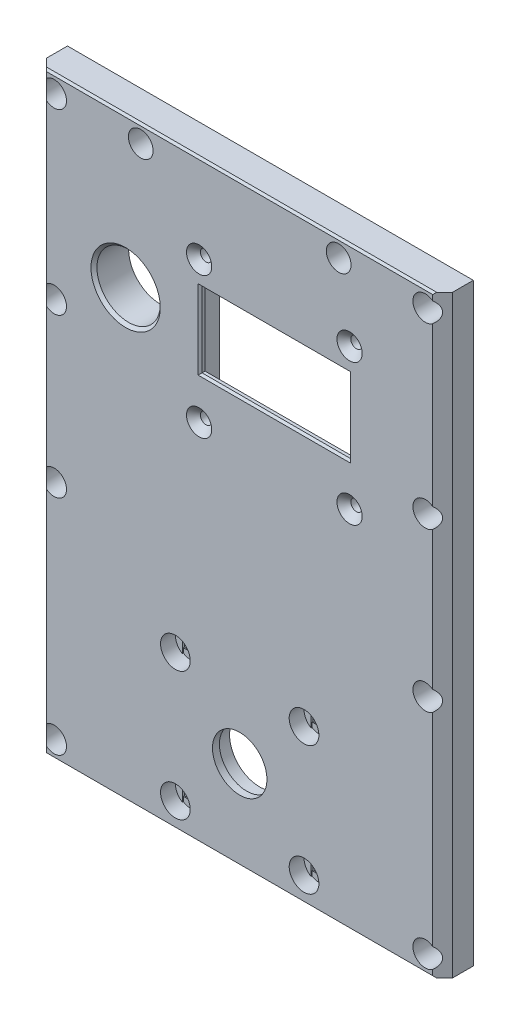
SolidWorks part; units mm, degrees
ref_plane "Front Plane" through (0, 0, 0) normal (0, 0, 1) x (1, 0, 0)
ref_plane "Top Plane" through (0, 0, 0) normal (0, 1, 0) x (1, 0, 0)
ref_plane "Right Plane" through (0, 0, 0) normal (1, 0, 0) x (0, 0, -1)
sketch "Sketch1" plane through (0, 0, 0) normal (0, 0, 1) x (1, 0, 0)
  line L1 (-41, -60) -> (41, -60)
  line L2 (-41, -60) -> (-41, 60)
  line L3 (-41, 60) -> (41, 60)
  line L4 (41, -60) -> (41, 60)
  line L5 (-41, -60) -> (41, 60) construction
  line L6 (-41, 60) -> (41, -60) construction
  line L7 (-34, -53) -> (34, -53)
  line L8 (-34, -53) -> (-34, 53)
  line L9 (-34, 53) -> (34, 53)
  line L10 (34, -53) -> (34, 53)
  line L11 (-34, -53) -> (34, 53) construction
  line L12 (-34, 53) -> (34, -53) construction
  point P0 (0, 0)
  point P6 (0, 0)
  dimension "D1" = 120
  dimension "D2" = 82
  dimension "D3" = 7
  dimension "D4" = 7
extrude "Boss-Extrude1" add sketch "Sketch1" along normal blind 7
sketch "Sketch2" plane through (0, 0, 7) normal (0, 0, 1) x (1, 0, 0)
  line L0 (34, -53) -> (34, 53) construction
  line L1 (-34, -53) -> (34, -53)
  line L2 (-34, -53) -> (-34, -17)
  line L3 (-34, -17) -> (34, -17)
  line L4 (34, -53) -> (34, -17)
  dimension "D1" = 36
extrude "Boss-Extrude2" add sketch "Sketch2" against normal up to surface (7 mm away) up to face at (0, 0, 0)
sketch "Sketch3" plane through (0, 0, 0) normal (0, 0, -1) x (-1, 0, 0)
  line L0 (0, -60) -> (0, -42) construction
  line L1 (41, -60) -> (-41, -60) construction
  circle A0 centre (0, -42) radius 5.5
  dimension "D1" = 11
  dimension "D2" = 18
extrude "Cut-Extrude1" cut sketch "Sketch3" against normal through all
sketch "Sketch4" plane through (0, 0, 0) normal (0, 0, -1) x (-1, 0, 0)
  circle A0 centre (0, -42) radius 6.05
  dimension "D1" = 12.1
extrude "Cut-Extrude2" cut sketch "Sketch4" against normal offset from surface (5.6 mm away) 1.4 up to face at (-5.5, -42, 7)
sketch "Sketch5" plane through (0, 0, 0) normal (0, 0, -1) x (-1, 0, 0)
  circle A0 centre (0, -42) radius 11.1
  dimension "D1" = 22.2
extrude "Cut-Extrude3" cut sketch "Sketch5" against normal offset from surface (3 mm away) 2.6 up to face at (-6.05, -42, 5.6)
sketch "Sketch6" plane through (0, 0, 0) normal (0, 0, -1) x (-1, 0, 0)
  line L1 (-13, -55) -> (13, -55) construction
  line L2 (-13, -55) -> (-13, -29) construction
  line L3 (-13, -29) -> (13, -29) construction
  line L4 (13, -55) -> (13, -29) construction
  line L5 (-13, -55) -> (13, -29) construction
  line L6 (-13, -29) -> (13, -55) construction
  circle A0 centre (-13, -29) radius 1.6
  circle A1 centre (13, -29) radius 1.6
  circle A2 centre (13, -55) radius 1.6
  circle A3 centre (-13, -55) radius 1.6
  point P0 (0, -42)
  dimension "D2" = 3.2
  dimension "D1" = 26
extrude "Cut-Extrude4" cut sketch "Sketch6" against normal through all
sketch "Sketch7" plane through (0, 0, 0) normal (0, 0, -1) x (-1, 0, 0)
  line L1 (-25, -61) -> (25, -61)
  line L2 (-25, -61) -> (-25, -23)
  line L3 (-25, -23) -> (25, -23)
  line L4 (25, -61) -> (25, -23)
  line L5 (-25, -61) -> (25, -23) construction
  line L6 (-25, -23) -> (25, -61) construction
  point P0 (0, -42)
  dimension "D1" = 50
  dimension "D2" = 38
extrude "Cut-Extrude5" cut sketch "Sketch7" against normal blind 1
sketch "Sketch8" plane through (0, 0, 7) normal (0, 0, 1) x (1, 0, 0)
  circle A0 centre (-13, -29) radius 3
  circle A1 centre (13, -29) radius 3
  circle A2 centre (13, -55) radius 3
  circle A3 centre (-13, -55) radius 3
  dimension "D1" = 6
extrude "Cut-Extrude6" cut sketch "Sketch8" against normal blind 3
sketch "Sketch9" plane through (0, 0, 7) normal (0, 0, 1) x (1, 0, 0)
  line L0 (-41, 60) -> (-41, -60) construction
  line L1 (-37.5, -56.5) -> (37.5, -56.5) construction
  line L2 (-37.5, -56.5) -> (-37.5, 56.5) construction
  line L3 (-37.5, 56.5) -> (37.5, 56.5) construction
  line L4 (37.5, -56.5) -> (37.5, 56.5) construction
  line L5 (-37.5, -56.5) -> (37.5, 56.5) construction
  line L6 (-37.5, 56.5) -> (37.5, -56.5) construction
  line L7 (41, 60) -> (-41, 60) construction
  circle A0 centre (-37.5, 56.5) radius 1.45
  circle A1 centre (37.5, 56.5) radius 1.45
  circle A2 centre (37.5, -56.5) radius 1.45
  circle A3 centre (-37.5, -56.5) radius 1.45
  circle A6 centre (-37.5, 20.5) radius 1.45
  circle A7 centre (-37.5, -11.5) radius 1.45
  circle A8 centre (37.5, -11.5) radius 1.45
  circle A9 centre (37.5, 20.5) radius 1.45
  point P0 (0, 0)
  dimension "D3" = 2.9
  dimension "D4" = 45
  dimension "D5" = 36
  dimension "D1" = 3.5
  dimension "D2" = 3.5
extrude "Cut-Extrude7" cut sketch "Sketch9" against normal through all
sketch "Sketch10" plane through (0, 0, 7) normal (0, 0, 1) x (1, 0, 0)
  circle A0 centre (-37.5, 56.5) radius 2.5
  circle A1 centre (37.5, 56.5) radius 2.5
  circle A2 centre (-37.5, 20.5) radius 2.5
  circle A3 centre (-37.5, -11.5) radius 2.5
  circle A4 centre (-37.5, -56.5) radius 2.5
  circle A5 centre (37.5, -56.5) radius 2.5
  circle A6 centre (37.5, 20.5) radius 2.5
  circle A7 centre (37.5, -11.5) radius 2.5
  dimension "D1" = 5
extrude "Cut-Extrude8" cut sketch "Sketch10" against normal blind 5
chamfer "Chamfer1" distance 2 angle 45 2 edges at (-41, 0, 7) (41, 0, 7)
sketch "Sketch11" plane through (0, 0, 7) normal (0, 0, 1) x (1, 0, 0)
  line L0 (34, -17) -> (34, 53) construction
  line L1 (-34, -17) -> (34, -17)
  line L2 (-34, -17) -> (-34, 2)
  line L3 (-34, 2) -> (34, 2)
  line L4 (34, -17) -> (34, 2)
  line L5 (-39, -60) -> (39, -60) construction
  dimension "D1" = 62
extrude "Boss-Extrude3" add sketch "Sketch11" against normal up to surface (7 mm away) up to face at (38.95, 56.5, 0)
sketch "Sketch12" plane through (0, 0, 2) normal (0, 0, 1) x (1, 0, 0)
  line L2 (-38.95, -58.5365) -> (-38.95, -54.4635)
  line L4 (-36.05, -58.5365) -> (-36.05, -54.4635)
  line L5 (-38.95, -58.5365) -> (-36.05, -54.4635) construction
  line L6 (-38.95, -54.4635) -> (-36.05, -58.5365) construction
  line L8 (-38.95, -13.5365) -> (-38.95, -9.4635)
  line L10 (-36.05, -13.5365) -> (-36.05, -9.4635)
  line L11 (-38.95, -13.5365) -> (-36.05, -9.4635) construction
  line L12 (-38.95, -9.4635) -> (-36.05, -13.5365) construction
  line L14 (-38.95, 18.4635) -> (-38.95, 22.5365)
  line L16 (-36.05, 18.4635) -> (-36.05, 22.5365)
  line L17 (-38.95, 18.4635) -> (-36.05, 22.5365) construction
  line L18 (-38.95, 22.5365) -> (-36.05, 18.4635) construction
  line L20 (-38.95, 54.4635) -> (-38.95, 58.5365)
  line L22 (-36.05, 54.4635) -> (-36.05, 58.5365)
  line L23 (-38.95, 54.4635) -> (-36.05, 58.5365) construction
  line L24 (-38.95, 58.5365) -> (-36.05, 54.4635) construction
  arc A0 (-39, -58.5) -> (-39, -54.5) centre (-37.5, -56.5) ccw construction
  circle A1 centre (-37.5, -11.5) radius 2.5 construction
  circle A2 centre (-37.5, 20.5) radius 2.5 construction
  arc A3 (-39, 54.5) -> (-39, 58.5) centre (-37.5, 56.5) ccw construction
  circle A4 centre (-37.5, 56.5) radius 1.45 construction
  circle A5 centre (-37.5, 56.5) radius 2.5 construction
  arc A6 (-36.05, 58.5365) -> (-38.95, 58.5365) centre (-37.5, 56.5) ccw
  arc A7 (-38.95, 54.4635) -> (-36.05, 54.4635) centre (-37.5, 56.5) ccw
  circle A8 centre (-37.5, 20.5) radius 1.45 construction
  arc A9 (-38.95, 18.4635) -> (-36.05, 18.4635) centre (-37.5, 20.5) ccw
  arc A10 (-36.05, 22.5365) -> (-38.95, 22.5365) centre (-37.5, 20.5) ccw
  circle A11 centre (-37.5, -11.5) radius 1.45 construction
  arc A12 (-38.95, -13.5365) -> (-36.05, -13.5365) centre (-37.5, -11.5) ccw
  arc A13 (-36.05, -9.4635) -> (-38.95, -9.4635) centre (-37.5, -11.5) ccw
  circle A14 centre (-37.5, -56.5) radius 1.45 construction
  arc A16 (-38.95, -58.5365) -> (-36.05, -58.5365) centre (-37.5, -56.5) ccw
  arc A18 (-36.05, -54.4635) -> (-38.95, -54.4635) centre (-37.5, -56.5) ccw
  point P0 (-37.5, -56.5)
  point P9 (-37.5, -11.5)
  point P17 (-37.5, 20.5)
  point P25 (-37.5, 56.5)
extrude "Cut-Extrude9" cut sketch "Sketch12" against normal blind 0.2
sketch "Sketch13" plane through (0, 0, 1.8) normal (0, 0, 1) x (1, 0, 0)
  line L0 (-36.05, -56.5) -> (-36.05, -54.4635) construction
  line L1 (-38.95, -57.95) -> (-36.05, -57.95)
  line L2 (-38.95, -57.95) -> (-38.95, -55.05)
  line L3 (-38.95, -55.05) -> (-36.05, -55.05)
  line L4 (-36.05, -57.95) -> (-36.05, -55.05)
  line L5 (-38.95, -57.95) -> (-36.05, -55.05) construction
  line L6 (-38.95, -55.05) -> (-36.05, -57.95) construction
  line L7 (-36.05, -11.5) -> (-36.05, -9.4635) construction
  line L8 (-38.95, -12.95) -> (-36.05, -12.95)
  line L9 (-38.95, -12.95) -> (-38.95, -10.05)
  line L10 (-38.95, -10.05) -> (-36.05, -10.05)
  line L11 (-36.05, -12.95) -> (-36.05, -10.05)
  line L12 (-38.95, -12.95) -> (-36.05, -10.05) construction
  line L13 (-38.95, -10.05) -> (-36.05, -12.95) construction
  line L14 (-36.05, 18.4635) -> (-36.05, 22.5365) construction
  line L15 (-38.95, 19.05) -> (-36.05, 19.05)
  line L16 (-38.95, 19.05) -> (-38.95, 21.95)
  line L17 (-38.95, 21.95) -> (-36.05, 21.95)
  line L18 (-36.05, 19.05) -> (-36.05, 21.95)
  line L19 (-38.95, 19.05) -> (-36.05, 21.95) construction
  line L20 (-38.95, 21.95) -> (-36.05, 19.05) construction
  line L21 (-36.05, 54.4635) -> (-36.05, 58.5365) construction
  line L22 (-38.95, 55.05) -> (-36.05, 55.05)
  line L23 (-38.95, 55.05) -> (-38.95, 57.95)
  line L24 (-38.95, 57.95) -> (-36.05, 57.95)
  line L25 (-36.05, 55.05) -> (-36.05, 57.95)
  line L26 (-38.95, 55.05) -> (-36.05, 57.95) construction
  line L27 (-38.95, 57.95) -> (-36.05, 55.05) construction
  arc A0 (-36.05, -56.5) -> (-38.95, -56.5) centre (-37.5, -56.5) ccw construction
  arc A1 (-36.05, -11.5) -> (-38.95, -11.5) centre (-37.5, -11.5) ccw construction
  arc A2 (-36.05, 20.5) -> (-38.95, 20.5) centre (-37.5, 20.5) ccw construction
  arc A3 (-36.05, 56.5) -> (-38.95, 56.5) centre (-37.5, 56.5) ccw construction
  point P0 (-37.5, -56.5)
  point P11 (-37.5, -11.5)
  point P22 (-37.5, 20.5)
  point P33 (-37.5, 56.5)
extrude "Cut-Extrude10" cut sketch "Sketch13" against normal blind 0.2
sketch "Sketch14" plane through (0, 0, 4) normal (0, 0, 1) x (1, 0, 0)
  line L2 (-14.6, -31.5377) -> (-14.6, -26.4623)
  line L4 (-11.4, -31.5377) -> (-11.4, -26.4623)
  line L5 (-14.6, -31.5377) -> (-11.4, -26.4623) construction
  line L6 (-14.6, -26.4623) -> (-11.4, -31.5377) construction
  line L8 (-14.6, -57.5377) -> (-14.6, -52.4623)
  line L10 (-11.4, -57.5377) -> (-11.4, -52.4623)
  line L11 (-14.6, -57.5377) -> (-11.4, -52.4623) construction
  line L12 (-14.6, -52.4623) -> (-11.4, -57.5377) construction
  circle A0 centre (-13, -29) radius 3 construction
  circle A1 centre (-13, -55) radius 3 construction
  circle A2 centre (-13, -29) radius 3 construction
  arc A3 (-14.6, -31.5377) -> (-11.4, -31.5377) centre (-13, -29) ccw
  arc A4 (-14.6, -57.5377) -> (-11.4, -57.5377) centre (-13, -55) ccw
  circle A5 centre (-13, -29) radius 1.6 construction
  circle A6 centre (-13, -55) radius 1.6 construction
  arc A7 (-11.4, -26.4623) -> (-14.6, -26.4623) centre (-13, -29) ccw
  arc A8 (-11.4, -52.4623) -> (-14.6, -52.4623) centre (-13, -55) ccw
  point P0 (-13, -29)
  point P8 (-13, -55)
extrude "Cut-Extrude11" cut sketch "Sketch14" against normal blind 0.2
sketch "Sketch15" plane through (0, 0, 3.8) normal (0, 0, 1) x (1, 0, 0)
  line L0 (-11.4, -29) -> (-11.4, -26.4623) construction
  line L1 (-14.6, -30.6) -> (-11.4, -30.6)
  line L2 (-14.6, -30.6) -> (-14.6, -27.4)
  line L3 (-14.6, -27.4) -> (-11.4, -27.4)
  line L4 (-11.4, -30.6) -> (-11.4, -27.4)
  line L5 (-14.6, -30.6) -> (-11.4, -27.4) construction
  line L6 (-14.6, -27.4) -> (-11.4, -30.6) construction
  line L7 (-11.4, -55) -> (-11.4, -52.4623) construction
  line L8 (-14.6, -56.6) -> (-11.4, -56.6)
  line L9 (-14.6, -56.6) -> (-14.6, -53.4)
  line L10 (-14.6, -53.4) -> (-11.4, -53.4)
  line L11 (-11.4, -56.6) -> (-11.4, -53.4)
  line L12 (-14.6, -56.6) -> (-11.4, -53.4) construction
  line L13 (-14.6, -53.4) -> (-11.4, -56.6) construction
  arc A0 (-11.4, -55) -> (-14.6, -55) centre (-13, -55) ccw construction
  arc A1 (-14.6, -29) -> (-11.4, -29) centre (-13, -29) ccw construction
  point P0 (-13, -29)
  point P8 (-13, -55)
extrude "Cut-Extrude12" cut sketch "Sketch15" against normal blind 0.2
mirror "Mirror1" about plane through (0, 0, 0) normal (1, 0, 0) of "Cut-Extrude10", "Cut-Extrude11", "Cut-Extrude12", "Cut-Extrude9"
chamfer "Chamfer2" distance 0.4 angle 45 4 edges at (34, 27.5, 7) (0, 53, 7) (0, 2, 7) (-34, 27.5, 7)
chamfer "Chamfer3" distance 0.8 angle 45 2 edges at (-41, 0, 0) (41, 0, 0)
sketch "Sketch16" plane through (0, 0, 0) normal (1, 0, 0) x (0, 0, -1)
  line L0 (0, -4) -> (0, -15.4)
  line L1 (0, 60) -> (0, -60) construction
  line L2 (0, -15.4) -> (3.2, -12.2)
  line L3 (3.2, -12.2) -> (3.2, -7.2)
  line L4 (3.2, -7.2) -> (0, -4)
  line L5 (0, -15.4) -> (0, -19.4) construction
  line L6 (0.6, -7.7) -> (2.6, -7.7)
  line L7 (0.6, -7.7) -> (0.6, -11.7)
  line L8 (0.6, -11.7) -> (2.6, -11.7)
  line L9 (2.6, -7.7) -> (2.6, -11.7)
  line L10 (-1.046, -17.4) -> (12.8392, -17.4) construction
  line L11 (2.6, -27.1) -> (2.6, -23.1)
  line L12 (0.6, -23.1) -> (2.6, -23.1)
  line L13 (0.6, -27.1) -> (0.6, -23.1)
  line L14 (0.6, -27.1) -> (2.6, -27.1)
  line L15 (3.2, -27.6) -> (0, -30.8)
  line L16 (3.2, -22.6) -> (3.2, -27.6)
  line L17 (0, -19.4) -> (3.2, -22.6)
  line L18 (0, -30.8) -> (0, -19.4)
  point P10 (2.6, -9.7)
  point P11 (3.2, -9.7)
  point P24 (0, -17.4)
  dimension "D1" = 5
  dimension "D2" = 2
  dimension "D3" = 0.6
  dimension "D4" = 0.6
  dimension "D5" = 45
  dimension "D6" = 4
  dimension "D7" = 4
  dimension "D8" = 4
extrude "Boss-Extrude4" add sketch "Sketch16" along normal mid plane 2
pattern_linear "LPattern1" count 2 spacing 20 along (1, 0, 0) count 2 spacing 20 along (-1, 0, 0) of "Boss-Extrude4"
sketch "Sketch17" plane through (0, 0, 0) normal (0, 0, -1) x (-1, 0, 0)
  line L0 (-20, 56.5) -> (20, 56.5) construction
  line L1 (-40.2, 60) -> (40.2, 60) construction
  circle A0 centre (-37.5, 56.5) radius 1.45 construction
  circle A1 centre (-37.5, 56.5) radius 1.45 construction
  circle A2 centre (-20, 56.5) radius 1.45
  circle A3 centre (20, 56.5) radius 1.45
  point P3 (0, 56.5)
  point P6 (0, 60)
  dimension "D1" = 40
extrude "Cut-Extrude13" cut sketch "Sketch17" against normal through all
sketch "Sketch18" plane through (0, 0, 7) normal (0, 0, 1) x (1, 0, 0)
  circle A0 centre (-20, 56.5) radius 2.5
  circle A1 centre (20, 56.5) radius 2.5
  arc A2 (-39, 54.5) -> (-39, 58.5) centre (-37.5, 56.5) ccw construction
extrude "Cut-Extrude14" cut sketch "Sketch18" against normal up to surface (5 mm away) up to face at (35.525, 56.5, 2)
sketch "Sketch19" plane through (0, 0, 2) normal (0, 0, 1) x (1, 0, 0)
  line L2 (-21.45, 54.4635) -> (-21.45, 58.5365)
  line L4 (-18.55, 54.4635) -> (-18.55, 58.5365)
  line L5 (-21.45, 54.4635) -> (-18.55, 58.5365) construction
  line L6 (-21.45, 58.5365) -> (-18.55, 54.4635) construction
  line L8 (18.55, 54.4635) -> (18.55, 58.5365)
  line L10 (21.45, 54.4635) -> (21.45, 58.5365)
  line L11 (18.55, 54.4635) -> (21.45, 58.5365) construction
  line L12 (18.55, 58.5365) -> (21.45, 54.4635) construction
  circle A0 centre (-20, 56.5) radius 2.5 construction
  circle A1 centre (20, 56.5) radius 2.5 construction
  circle A2 centre (20, 56.5) radius 1.45 construction
  circle A3 centre (-20, 56.5) radius 1.45 construction
  circle A4 centre (-20, 56.5) radius 2.5 construction
  arc A5 (18.55, 54.4635) -> (21.45, 54.4635) centre (20, 56.5) ccw
  arc A6 (-18.55, 58.5365) -> (-21.45, 58.5365) centre (-20, 56.5) ccw
  arc A7 (21.45, 58.5365) -> (18.55, 58.5365) centre (20, 56.5) ccw
  arc A8 (-21.45, 54.4635) -> (-18.55, 54.4635) centre (-20, 56.5) ccw
  point P0 (-20, 56.5)
  point P8 (20, 56.5)
extrude "Cut-Extrude15" cut sketch "Sketch19" against normal blind 0.2
sketch "Sketch20" plane through (0, 0, 1.8) normal (0, 0, 1) x (1, 0, 0)
  line L0 (-18.55, 54.4635) -> (-18.55, 58.5365) construction
  line L1 (-21.45, 55.05) -> (-18.55, 55.05)
  line L2 (-21.45, 55.05) -> (-21.45, 57.95)
  line L3 (-21.45, 57.95) -> (-18.55, 57.95)
  line L4 (-18.55, 55.05) -> (-18.55, 57.95)
  line L5 (-21.45, 55.05) -> (-18.55, 57.95) construction
  line L6 (-21.45, 57.95) -> (-18.55, 55.05) construction
  line L7 (21.45, 56.5) -> (21.45, 58.5365) construction
  line L8 (18.55, 55.05) -> (21.45, 55.05)
  line L9 (18.55, 55.05) -> (18.55, 57.95)
  line L10 (18.55, 57.95) -> (21.45, 57.95)
  line L11 (21.45, 55.05) -> (21.45, 57.95)
  line L12 (18.55, 55.05) -> (21.45, 57.95) construction
  line L13 (18.55, 57.95) -> (21.45, 55.05) construction
  arc A0 (18.55, 56.5) -> (21.45, 56.5) centre (20, 56.5) ccw construction
  point P0 (-20, 56.5)
  point P8 (20, 56.5)
extrude "Cut-Extrude16" cut sketch "Sketch20" against normal blind 0.2
sketch "Skizze4" plane through (0, 0, 0) normal (0, 0, -1) x (-1, 0, 0)
  line L1 (21, -4) -> (-21, -4)
  line L2 (21, -4) -> (21, -30.8)
  line L3 (21, -30.8) -> (-21, -30.8)
  line L4 (-21, -4) -> (-21, -30.8)
extrude "Schnitt-Linear austragen1" cut sketch "Skizze4" along normal up to surface (3.2 mm away) up to face at (-20, -9.7, -3.2)
sketch "Skizze6" plane through (0, 0, 7) normal (0, 0, 1) x (1, 0, 0)
  line L0 (12.4, 53.4) -> (34.4, 31.4) construction
  line L1 (34.4, 53.4) -> (12.4, 53.4)
  line L2 (34.4, 53.4) -> (34.4, 31.4)
  line L3 (34.4, 31.4) -> (12.4, 31.4)
  line L4 (12.4, 53.4) -> (12.4, 31.4)
  line L5 (23.4, 53.4) -> (23.4, 31.4) construction
  circle A0 centre (23.4, 41.4) radius 8.25
  point P10 (23.4, 42.4)
  dimension "D1" = 16.5
  dimension "D2" = 22
  dimension "D3" = 22
  dimension "D4" = 1
extrude "Aufsatz-Linear austragen1" add sketch "Skizze6" against normal up to surface (7 mm away) up to face at (0, -20.75, 0)
sketch "Skizze7" plane through (0, 0, 7) normal (0, 0, 1) x (1, 0, 0)
  circle A0 centre (23.4, 41.4) radius 9.25
  dimension "D1" = 18.5
extrude "Schnitt-Linear austragen2" cut sketch "Skizze7" against normal blind 1.6
chamfer "Fase6" distance 0.5 angle 45 2 edges at (12.4, 42.4, 7) (23.4, 31.4, 7)
chamfer "Fase7" distance 4 angle 45 1 edges at (12.4, 31.4, 3.25)
chamfer "Fase8" distance 1 angle 45 1 edges at (31.65, 41.4, 5.4)
mirror "Mirror2" about plane through (0, 0, 0) normal (1, 0, 0) of "Fase6", "Schnitt-Linear austragen2", "Fase8", "Aufsatz-Linear austragen1", "Fase7"
sketch "Sketch21" plane through (0, 0, 7) normal (0, 0, 1) x (1, 0, 0)
  line L0 (34.4, 31.9) -> (34.4, 1.6) construction
  line L1 (-34.4, 31.9) -> (-15.9, 31.9)
  line L2 (-34.4, 31.9) -> (-34.4, 15.9)
  line L3 (-34.4, 15.9) -> (34.4, 15.9)
  line L4 (34.4, 31.9) -> (34.4, 15.9)
  line L5 (-15.9, 31.9) -> (-12.4, 35.4)
  line L6 (-12.4, 35.4) -> (-12.4, 31.9)
  line L7 (12.4, 35.4) -> (15.9, 31.9)
  line L8 (12.4, 35.4) -> (12.4, 31.9)
  line L9 (-12.4, 31.9) -> (12.4, 31.9)
  line L10 (15.9, 31.9) -> (34.4, 31.9)
  dimension "D1" = 16
extrude "Boss-Extrude5" add sketch "Sketch21" against normal up to surface (7 mm away) up to face at (0, 30.64, 0)
chamfer "Chamfer4" distance 0.5 angle 45 7 edges at (12.65, 35.15, 7) (12.4, 33.65, 7) (0, 31.9, 7) (-12.4, 33.65, 7) (-12.65, 35.15, 7) (12.4, 35.4, 6.75) (-12.4, 35.4, 6.75)
sketch "Sketch22" plane through (0, 0, 0) normal (0, 0, -1) x (-1, 0, 0)
  line L0 (0, 31.9) -> (0, 15.9) construction
  line L1 (-12.4, 31.9) -> (12.4, 31.9) construction
  line L2 (34, 15.9) -> (-34, 15.9) construction
  line L4 (-18.95, 17.75) -> (18.95, 17.75)
  line L5 (-18.95, 17.75) -> (-18.95, 30.05)
  line L6 (-18.95, 30.05) -> (18.95, 30.05)
  line L7 (18.95, 17.75) -> (18.95, 30.05)
  line L8 (-18.95, 17.75) -> (18.95, 30.05) construction
  line L9 (-18.95, 30.05) -> (18.95, 17.75) construction
  point P6 (0, 23.9)
  dimension "D1" = 37.9
  dimension "D2" = 12.3
extrude "Cut-Extrude17" cut sketch "Sketch22" against normal offset from surface (6.4 mm away) 0.6 up to face at (0, 8.75, 7)
sketch "Sketch23" plane through (0, 0, 6.4) normal (0, 0, -1) x (-1, 0, 0)
  line L0 (-18.95, 30.05) -> (-18.95, 17.75) construction
  line L1 (-12.95, 18.55) -> (12.05, 18.55)
  line L2 (-12.95, 18.55) -> (-12.95, 28.55)
  line L3 (-12.95, 28.55) -> (12.05, 28.55)
  line L4 (12.05, 18.55) -> (12.05, 28.55)
  line L5 (-12.95, 18.55) -> (12.05, 28.55) construction
  line L6 (-12.95, 28.55) -> (12.05, 18.55) construction
  line L7 (-18.95, 30.05) -> (18.95, 30.05) construction
  point P0 (-0.45, 23.55)
  dimension "D1" = 25
  dimension "D2" = 10
  dimension "D3" = 6
  dimension "D4" = 1.5
extrude "Cut-Extrude18" cut sketch "Sketch23" against normal through all
chamfer "Chamfer5" distance 0.4 angle 45 1 edges at (0, 15.9, 7)
sketch "Sketch24" plane through (0, 0, 7) normal (0, 0, 1) x (1, 0, 0)
  line L1 (-12.9, 53.4) -> (12.9, 53.4)
  line L2 (-12.9, 53.4) -> (-12.9, 31.4)
  line L3 (-12.9, 31.4) -> (12.9, 31.4)
  line L4 (12.9, 53.4) -> (12.9, 31.4)
  line L5 (-12.4, 53) -> (12.4, 53)
  line L6 (-12.4, 53) -> (-12.4, 31.9)
  line L7 (-12.4, 31.9) -> (12.4, 31.9)
  line L8 (12.4, 53) -> (12.4, 31.9)
extrude "Boss-Extrude6" add sketch "Sketch24" against normal up to vertex (0.5 mm away) up to point (12.4, 31.9, 6.5)
chamfer "Chamfer7" distance 3 angle 45 4 edges at (12.4, 31.9, 3.5) (12.4, 53, 3.5) (-12.4, 53, 3.5) (-12.4, 31.9, 3.5)
chamfer "Chamfer8" distance 0.5 angle 45 8 edges at (12.4, 42.45, 7) (0, 31.9, 7) (0, 53, 7) (-12.4, 42.45, 7) (10.9, 33.4, 7) (10.9, 51.5, 7) (-10.9, 51.5, 7) (-10.9, 33.4, 7)
chamfer "Chamfer9" distance 0.8 angle 45 6 edges at (-34, 8.95, 0) (0, 15.9, 0) (34, 8.95, 0) (0, 2, 0) (-32.6, -60, 0) (0, 60, 0)
sketch "Sketch28" plane through (0, 0, 7) normal (0, 0, 1) x (1, 0, 0)
  circle A0 centre (23.4, 41.4) radius 10
  dimension "D1" = 20
extrude "Boss-Extrude8" add sketch "Sketch28" against normal up to surface (7 mm away) up to face at (0, 8.95, 0)
sketch "Sketch29" plane through (0, 0, 0) normal (0, 0, -1) x (-1, 0, 0)
  line L0 (-9.4, 53) -> (9.4, 53) construction
  line L1 (34.8, 53) -> (-34.8, 53)
  line L2 (34.8, 53) -> (34.8, 1.2)
  line L3 (34.8, 1.2) -> (-34.8, 1.2)
  line L4 (-34.8, 53) -> (-34.8, 1.2)
  line L5 (34.8, 1.2) -> (-34.8, 1.2) construction
  line L6 (34.8, 16.7) -> (34.8, 1.2) construction
  line L7 (-34.8, 1.2) -> (-34.8, 16.7) construction
extrude "Boss-Extrude9" add sketch "Sketch29" against normal up to surface (7 mm away) up to face at (0, 42.45, 7)
sketch "Sketch30" plane through (0, 0, 7) normal (0, 0, 1) x (1, 0, 0)
  line L0 (9.4, 53) -> (10.1071, 53) construction
  line L1 (10.1071, 53) -> (9.6071, 53.5) construction
  line L2 (-10.1071, 53) -> (-9.4, 53) construction
  line L3 (-9.6071, 53.5) -> (-10.1071, 53) construction
  line L4 (9.6071, 53.5) -> (-9.6071, 53.5) construction
  line L5 (-9.4, 53) -> (9.4, 53) construction
  line L6 (9.4, 53) -> (10.1071, 53)
  line L7 (10.1071, 53) -> (9.6071, 53.5)
  line L8 (-10.1071, 53) -> (-9.4, 53)
  line L9 (-9.6071, 53.5) -> (-10.1071, 53)
  line L10 (9.6071, 53.5) -> (-9.6071, 53.5)
  line L11 (-9.4, 53) -> (9.4, 53)
extrude "Boss-Extrude10" add sketch "Sketch30" against normal up to surface (7 mm away) up to face at (0, -20.75, 0)
sketch "Sketch31" plane through (0, 0, 0) normal (0, 0, -1) x (-1, 0, 0)
  line L0 (-7, 55.2531) -> (-7, 0.5469) construction
  line L1 (-24.8, 11.05) -> (10.8, 11.05) construction
  line L2 (-24.8, 11.05) -> (-24.8, 44.75) construction
  line L3 (-24.8, 44.75) -> (10.8, 44.75) construction
  line L4 (10.8, 11.05) -> (10.8, 44.75) construction
  line L5 (-24.8, 11.05) -> (10.8, 44.75) construction
  line L6 (-24.8, 44.75) -> (10.8, 11.05) construction
  line L7 (-22.2, 13.65) -> (8.2, 13.65) construction
  line L8 (-22.2, 13.65) -> (-22.2, 42.15) construction
  line L9 (-22.2, 42.15) -> (8.2, 42.15) construction
  line L10 (8.2, 13.65) -> (8.2, 42.15) construction
  line L11 (-22.2, 13.65) -> (8.2, 42.15) construction
  line L12 (-22.2, 42.15) -> (8.2, 13.65) construction
  line L13 (-25.05, 10.8) -> (11.05, 10.8)
  line L14 (-25.05, 10.8) -> (-25.05, 45)
  line L15 (-25.05, 45) -> (11.05, 45)
  line L16 (11.05, 10.8) -> (11.05, 45)
  line L17 (-25.05, 10.8) -> (11.05, 45) construction
  line L18 (-25.05, 45) -> (11.05, 10.8) construction
  line L19 (-22, 22.2) -> (8, 22.2) construction
  line L20 (-22, 22.2) -> (-22, 37.4) construction
  line L21 (-22, 37.4) -> (8, 37.4) construction
  line L22 (8, 22.2) -> (8, 37.4) construction
  line L23 (-22, 22.2) -> (8, 37.4) construction
  line L24 (-22, 37.4) -> (8, 22.2) construction
  line L25 (-7, 29.8) -> (23, 29.8) construction
  line L26 (23, 17.8) -> (23, 41.8) construction
  line L27 (-41, -60) -> (-41, 60) construction
  line L28 (-41, 60) -> (41, 60) construction
  circle A0 centre (-22.2, 42.15) radius 1.5 construction
  circle A1 centre (8.2, 42.15) radius 1.5 construction
  circle A2 centre (8.2, 13.65) radius 1.5 construction
  circle A3 centre (-22.2, 13.65) radius 1.5 construction
  circle A4 centre (23, 41.8) radius 6.3
  circle A5 centre (23, 17.8) radius 6.3
  circle A6 centre (23, 17.8) radius 7
  circle A7 centre (23, 41.8) radius 7
  point P2 (-7, 27.9)
  point P7 (-7, 27.9)
  point P16 (-7, 27.9)
  point P21 (-7, 29.8)
  point P32 (23, 29.8)
  point P40 (0, 60)
  dimension "D5" = 3
  dimension "D12" = 15
  dimension "D13" = 12.6
  dimension "D14" = 14
  dimension "D1" = 35.6
  dimension "D2" = 33.7
  dimension "D3" = 30.4
  dimension "D4" = 28.5
  dimension "D6" = 0.25
  dimension "D7" = 0.25
  dimension "D8" = 15.2
  dimension "D9" = 30
  dimension "D10" = 7.35
  dimension "D11" = 34
  dimension "D15" = 24
  dimension "D16" = 30
sketch "Sketch32" plane through (0, 0, 0) normal (0, 0, -1) x (-1, 0, 0)
  line L0 (-25.05, 10.8) -> (-25.05, 45) construction
  line L1 (-25.05, 10.8) -> (11.05, 10.8) construction
  line L2 (11.05, 10.8) -> (11.05, 45) construction
  line L3 (-25.05, 45) -> (11.05, 45) construction
  line L4 (-25.05, 10.8) -> (-25.05, 45)
  line L5 (-25.05, 10.8) -> (11.05, 10.8)
  line L6 (11.05, 10.8) -> (11.05, 45)
  line L7 (-25.05, 45) -> (11.05, 45)
extrude "Cut-Extrude19" cut sketch "Sketch32" against normal offset from surface (6 mm away) 1 up to face at (-17.5, 56.5, 7)
sketch "Sketch33" plane through (0, 0, 6) normal (0, 0, -1) x (-1, 0, 0)
  line L0 (-22, 22.2) -> (-22, 37.4) construction
  line L1 (-22, 22.2) -> (8, 22.2) construction
  line L2 (8, 22.2) -> (8, 37.4) construction
  line L3 (-22, 37.4) -> (8, 37.4) construction
  line L4 (-22, 22.2) -> (-22, 37.4)
  line L5 (-22, 22.2) -> (8, 22.2)
  line L6 (8, 22.2) -> (8, 37.4)
  line L7 (-22, 37.4) -> (8, 37.4)
extrude "Cut-Extrude20" cut sketch "Sketch33" against normal through all
sketch "Sketch35" plane through (0, 0, 6) normal (0, 0, -1) x (-1, 0, 0)
  line L1 (-25.05, 10.8) -> (-20.2, 10.8)
  line L2 (-25.05, 10.8) -> (-25.05, 15.65)
  line L3 (-25.05, 15.65) -> (-20.2, 15.65)
  line L4 (-20.2, 10.8) -> (-20.2, 15.65)
  line L5 (11.05, 10.8) -> (6.2, 10.8)
  line L6 (11.05, 10.8) -> (11.05, 15.65)
  line L7 (11.05, 15.65) -> (6.2, 15.65)
  line L8 (6.2, 10.8) -> (6.2, 15.65)
  line L9 (-25.05, 45) -> (-20.2, 45)
  line L10 (-25.05, 45) -> (-25.05, 40.15)
  line L11 (-25.05, 40.15) -> (-20.2, 40.15)
  line L12 (-20.2, 45) -> (-20.2, 40.15)
  line L13 (11.05, 45) -> (6.2, 45)
  line L14 (11.05, 45) -> (11.05, 40.15)
  line L15 (11.05, 40.15) -> (6.2, 40.15)
  line L16 (6.2, 45) -> (6.2, 40.15)
  dimension "D1" = 2
  dimension "D2" = 2
  dimension "D3" = 2
  dimension "D4" = 2
extrude "Boss-Extrude11" add sketch "Sketch35" along normal blind 1.8
sketch "Sketch36" plane through (0, 0, 4.2) normal (0, 0, -1) x (-1, 0, 0)
  circle A0 centre (-22.2, 13.65) radius 1.15
  circle A1 centre (8.2, 13.65) radius 1.15
  circle A2 centre (8.2, 42.15) radius 1.15
  circle A3 centre (-22.2, 42.15) radius 1.15
  dimension "D1" = 2.3
extrude "Cut-Extrude22" cut sketch "Sketch36" against normal through all
chamfer "Chamfer10" distance 1.4 angle 45 4 edges at (-9.35, 13.65, 7) (21.05, 13.65, 7) (21.05, 42.15, 7) (-9.35, 42.15, 7)
sketch "Sketch37" plane through (0, 0, 0) normal (0, 0, -1) x (-1, 0, 0)
  line L0 (8, 22.2) -> (8, 37.4) construction
  line L1 (11.05, 10.8) -> (11.05, 45) construction
  circle A0 centre (23.05, 29.8) radius 6.4
  point P2 (0, 0)
  point P5 (8, 29.8)
  dimension "D1" = 12.8
  dimension "D2" = 12
extrude "Cut-Extrude23" cut sketch "Sketch37" against normal through all
chamfer "Chamfer11" distance 0.6 angle 45 1 edges at (-29.45, 29.8, 7)
chamfer "Chamfer12" distance 0.4 angle 45 4 edges at (7, 22.2, 7) (22, 29.8, 7) (-8, 29.8, 7) (7, 37.4, 7)
chamfer "Chamfer13" distance 0.4 angle 45 2 edges at (0, -60, 7) (0, 60, 7)
